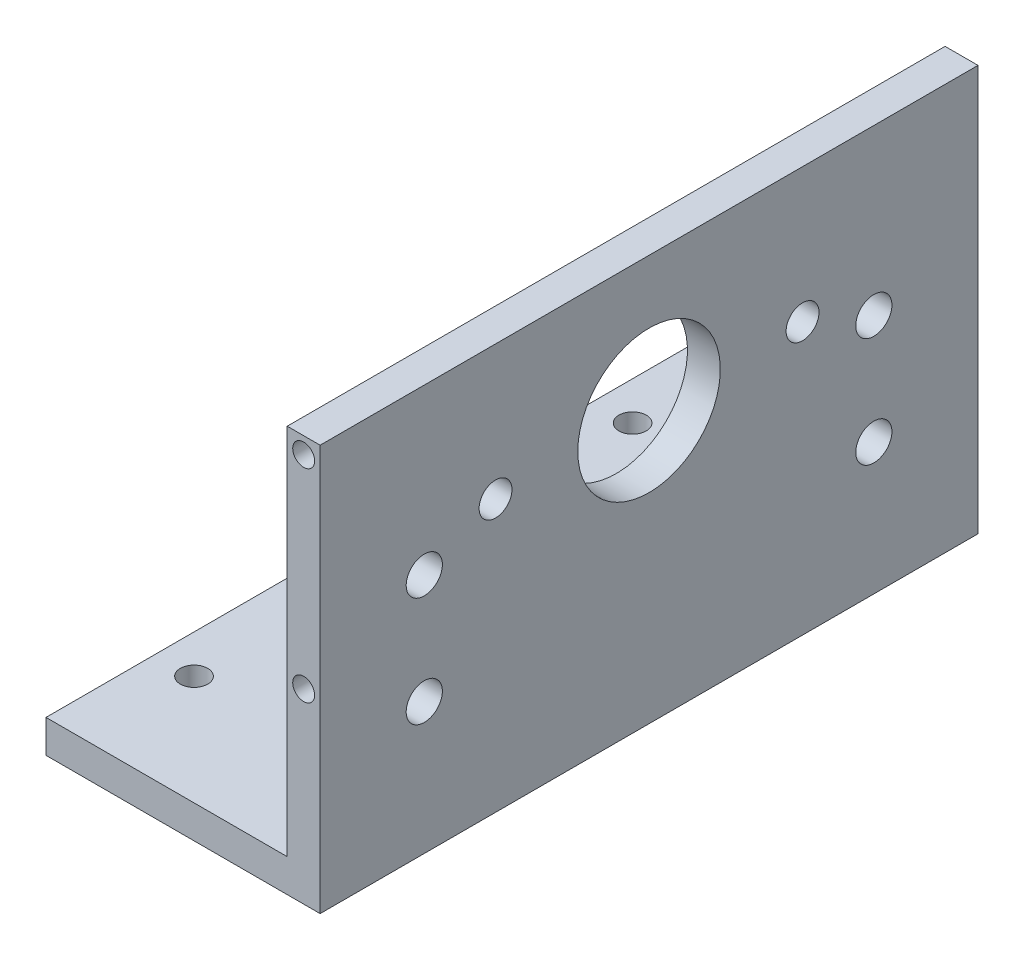
SolidWorks part; units mm, degrees
material "6061 合金"
ref_plane "前视基准面" through (0, 0, 0) normal (0, 0, 1) x (1, 0, 0)
ref_plane "上视基准面" through (0, 0, 0) normal (0, 1, 0) x (1, 0, 0)
ref_plane "右视基准面" through (0, 0, 0) normal (1, 0, 0) x (0, 0, -1)
sketch "草图1" plane through (0, 0, 0) normal (0, 1, 0) x (1, 0, 0)
  line L1 (-25, -60) -> (25, -60)
  line L2 (-25, -60) -> (-25, 60)
  line L3 (-25, 60) -> (25, 60)
  line L4 (25, -60) -> (25, 60)
  line L5 (-25, -60) -> (25, 60) construction
  line L6 (-25, 60) -> (25, -60) construction
  line L7 (25, 60) -> (19, 60)
  line L8 (25, 60) -> (25, -60)
  line L9 (25, -60) -> (19, -60)
  line L10 (19, 60) -> (19, -60)
  point P0 (0, 0)
  dimension "D1" = 50
  dimension "D2" = 120
  dimension "D3" = 6
extrude "凸台-拉伸1" add sketch "草图1" along normal blind 6 contours L10 L3 L2 L1 region at (-3, 0, 0)
extrude "凸台-拉伸2" add sketch "草图1<3>" along normal blind 74 contours L3 L10 L1 L4 region at (22, 0, 0)
sketch "草图1<3>" plane through (0, 0, 0) normal (0, 1, 0) x (1, 0, 0) same geometry as "草图1"
sketch "草图2" plane through (19, 0, 0) normal (-1, 0, 0) x (0, 0, 1)
  line L0 (0, 6) -> (0, 74) construction
  line L1 (-60, 6) -> (60, 6) construction
  line L2 (-60, 74) -> (60, 74) construction
  line L3 (0, 49.5) -> (-60, 49.5) construction
  line L4 (0, 49.5) -> (28, 49.5) construction
  line L5 (-60, 74) -> (-60, 6) construction
  circle A0 centre (0, 49.5) radius 13
  circle A1 centre (-28, 49.5) radius 3
  circle A2 centre (28, 49.5) radius 3
  dimension "D1" = 26
  dimension "D2" = 43.5
  dimension "D3" = 6
  dimension "D4" = 28
  dimension "D5" = 60
extrude "切除-拉伸1" cut sketch "草图2" against normal through all
sketch "草图3" plane through (0, 6, 0) normal (0, 1, 0) x (1, 0, 0)
  line L0 (-25, -60) -> (-25, 60) construction
  line L1 (12, -40) -> (-18, -40) construction
  line L2 (12, -40) -> (12, 40) construction
  line L3 (12, 40) -> (-18, 40) construction
  line L4 (-18, -40) -> (-18, 40) construction
  line L5 (12, -40) -> (-18, 40) construction
  line L6 (12, 40) -> (-18, -40) construction
  circle A0 centre (-18, 40) radius 2.5
  circle A1 centre (12, 40) radius 2.5
  circle A2 centre (-18, -40) radius 2.5
  circle A3 centre (12, -40) radius 2.5
  point P0 (0, 0)
  dimension "D3" = 7
  dimension "D1" = 30
  dimension "D2" = 80
extrude "切除-拉伸2" cut sketch "草图3" against normal blind 10
sketch "草图4" plane through (0, 0, -60) normal (0, 0, -1) x (-1, 0, 0)
  line L0 (-19, 74) -> (-25, 74) construction
  circle A0 centre (-22, 34) radius 2
  circle A1 centre (-22, 71) radius 2
  dimension "D1" = 37
  dimension "D2" = 3
extrude "切除-拉伸3" cut sketch "草图4" against normal blind 20
ref_plane "基准面1" through (0, 0, 0) normal (0, 0, -1) x (-1, 0, 0)
mirror "镜向1" about plane through (0, 0, 0) normal (0, 0, -1) of "切除-拉伸3"
sketch "草图5" plane through (25, 0, 0) normal (1, 0, 0) x (0, 0, -1)
  line L0 (60, 34) -> (10.4302, 34) construction
  line L1 (60, 74) -> (60, 0) construction
  line L2 (-60, 0) -> (60, 0) construction
  line L3 (0, 49.5) -> (0, 0) construction
  circle A0 centre (41, 44) radius 3.3
  circle A1 centre (41, 24) radius 3.3
  circle A2 centre (-41, 24) radius 3.3
  circle A3 centre (-41, 44) radius 3.3
  dimension "D1" = 6.6
  dimension "D3" = 19
  dimension "D2" = 10
  dimension "D4" = 34
extrude "切除-拉伸4" cut sketch "草图5" against normal blind 10
